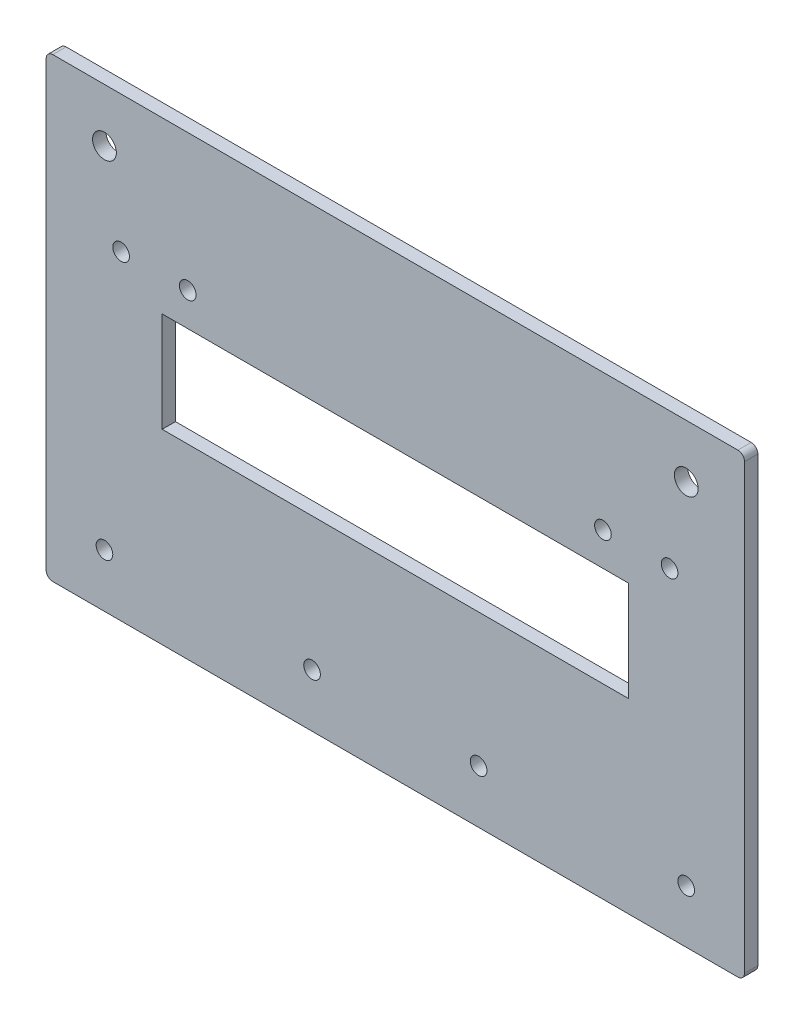
SolidWorks part; units mm, degrees
ref_plane "Front" through (0, 0, 0) normal (0, 0, 1) x (1, 0, 0)
ref_plane "Top" through (0, 0, 0) normal (0, 1, 0) x (1, 0, 0)
ref_plane "Right" through (0, 0, 0) normal (1, 0, 0) x (0, 0, -1)
sketch "Sketch1" plane through (0, 0, 0) normal (0, 0, 1) x (1, 0, 0)
  line L1 (0, 137) -> (209.64, 137)
  line L2 (0, 137) -> (0, 0)
  line L3 (0, 0) -> (209.64, 0)
  line L4 (209.64, 137) -> (209.64, 0)
  line L5 (52.5, 106) -> (52.5, 86)
  line L6 (52.5, 86) -> (34.82, 86)
  line L7 (34.82, 86) -> (34.82, 56)
  line L8 (34.82, 56) -> (174.82, 56)
  line L9 (174.82, 56) -> (174.82, 86)
  line L10 (174.82, 86) -> (157.14, 86)
  line L11 (157.14, 86) -> (157.14, 106)
  line L14 (157.14, 106) -> (52.5, 106)
  line L17 (104.82, 106) -> (104.82, 56) construction
  circle A0 centre (17.5, 16) radius 3.65
  circle A3 centre (192.14, 16) radius 3.65
  circle A5 centre (17.5, 121) radius 3.57
  circle A6 centre (42.5, 96) radius 2.5
  circle A7 centre (22.5, 96) radius 2.5
  circle A8 centre (192.14, 121) radius 3.57
  circle A9 centre (167.14, 96) radius 2.5
  circle A10 centre (187.14, 96) radius 2.5
  point P47 (52.5, 96)
  point P48 (157.14, 96)
  point P54 (104.82, 137)
  dimension "D3" = 5
  dimension "D4" = 5
  dimension "D5" = 5
  dimension "D6" = 5
  dimension "D13" = 7.3
  dimension "D14" = 7.3
  dimension "D17" = 7.14
  dimension "D18" = 7.14
  dimension "D1" = 20
  dimension "D2" = 20
  dimension "D11" = 20
  dimension "D19" = 10
  dimension "D20" = 10
  dimension "D24" = 30
  dimension "D26" = 17.5
  dimension "D29" = 17.5
  dimension "D30" = 16
  dimension "D31" = 16
  dimension "D9" = 140
  dimension "D10" = 104.64
  dimension "D7" = 25
  dimension "D12" = 40
  dimension "D8" = 5
extrude "Boss-Extrude1" add sketch "Sketch1" along normal blind 4
fillet "Fillet1" [suppressed] radius 2
sketch "Sketch2" plane through (0, 0, 4) normal (0, 0, 1) x (1, 0, 0)
  line L0 (11.5, 107) -> (11.5, 85)
  line L1 (11.5, 107) -> (49.82, 107)
  line L2 (11.5, 85) -> (34.82, 85)
  line L4 (198.14, 107) -> (198.14, 85)
  line L5 (52.5, 86) -> (34.82, 86) construction
  line L7 (198.14, 85) -> (174.82, 85)
  line L9 (157.14, 86) -> (157.14, 106) construction
  line L10 (52.5, 106) -> (52.5, 86) construction
  line L11 (34.82, 86) -> (34.82, 56) construction
  line L12 (174.82, 56) -> (174.82, 86) construction
  line L13 (49.82, 107) -> (49.82, 121)
  line L14 (49.82, 121) -> (159.82, 121)
  line L15 (159.82, 121) -> (159.82, 107)
  line L16 (159.82, 107) -> (198.14, 107)
  line L17 (34.82, 56) -> (174.82, 56) construction
  point P4 (104.82, 56)
  point P21 (104.82, 121)
  dimension "D3" = 41
  dimension "D2" = 1
  dimension "D4" = 41
  dimension "D1" = 14
  dimension "D5" = 110
  dimension "D6" = 22
extrude "Cut-Extrude1" [suppressed] cut sketch "Sketch2" against normal through all
sketch "Sketch3" plane through (0, 0, 4) normal (0, 0, 1) x (1, 0, 0)
  line L1 (52.5, 86) -> (157.14, 86)
  line L2 (52.5, 86) -> (52.5, 106)
  line L3 (52.5, 106) -> (157.14, 106)
  line L4 (157.14, 86) -> (157.14, 106)
extrude "Boss-Extrude2" add sketch "Sketch3" against normal blind 4
sketch "Sketch5" plane through (0, 0, 4) normal (0, 0, 1) x (1, 0, 0)
  line L0 (91.82, 48) -> (117.82, 48) construction
  line L1 (91.82, 48) -> (91.82, 22) construction
  line L3 (34.82, 56) -> (174.82, 56) construction
  line L5 (0, 0) -> (209.64, 0) construction
  circle A0 centre (104.82, 35) radius 11
  circle A1 centre (91.82, 48) radius 1.5
  circle A2 centre (117.82, 48) radius 1.5
  circle A3 centre (91.82, 22) radius 1.5
  circle A4 centre (117.82, 22) radius 1.5
  point P10 (104.82, 48)
  point P11 (91.82, 35)
  point P14 (104.82, 0)
  dimension "D3" = 22
  dimension "D1" = 26
  dimension "D2" = 26
  dimension "D4" = 8
extrude "Cut-Extrude3" [suppressed] cut sketch "Sketch5" against normal blind 4
sketch "Sketch6" plane through (0, 0, 4) normal (0, 0, 1) x (1, 0, 0)
  line L0 (79.82, 16) -> (129.82, 16) construction
  line L1 (0, 0) -> (209.64, 0) construction
  circle A0 centre (79.82, 16) radius 3.65
  circle A1 centre (129.82, 16) radius 3.65
  point P4 (104.82, 16)
  point P9 (104.82, 0)
  dimension "D2" = 7.3
  dimension "D3" = 7.3
  dimension "D1" = 50
extrude "Cut-Extrude4" cut sketch "Sketch6" against normal blind 4
sketch "Sketch7" [suppressed] plane through (0, 0, 4) normal (0, 0, 1) x (1, 0, 0)
  line L0 (0, 121) -> (0, 0) construction
  line L1 (209.64, 0) -> (209.64, 121) construction
  line L2 (34.82, 48) -> (174.82, 48) construction
  circle A0 centre (5, 43.5) radius 1.5
  circle A1 centre (5, 32.5) radius 1.5
  circle A2 centre (204.64, 43.5) radius 1.5
  circle A3 centre (204.64, 32.5) radius 1.5
  dimension "D3" = 5
  dimension "D4" = 3
  dimension "D5" = 3
  dimension "D6" = 3
  dimension "D7" = 3
  dimension "D1" = 5
  dimension "D2" = 11
  dimension "D8" = 4.5
extrude "Cut-Extrude5" [suppressed] cut sketch "Sketch7" against normal blind 10
sketch "Sketch8" [suppressed] plane through (0, 0, 4) normal (0, 0, 1) x (1, 0, 0)
  line L1 (34.82, 56) -> (174.82, 56)
  line L2 (34.82, 56) -> (34.82, 40)
  line L3 (34.82, 40) -> (174.82, 40)
  line L4 (174.82, 56) -> (174.82, 40)
  dimension "D1" = 16
extrude "Cut-Extrude6" [suppressed] cut sketch "Sketch8" against normal blind 10
fillet "Fillet2" [suppressed] radius 40
sketch "Sketch9" plane through (0, 0, 4) normal (0, 0, 1) x (1, 0, 0)
  line L0 (209.64, 137) -> (0, 137) construction
  line L1 (0, 137) -> (17, 137)
  line L2 (0, 137) -> (0, 130)
  line L3 (0, 130) -> (17, 130)
  line L4 (17, 137) -> (17, 130)
  line L5 (209.64, 137) -> (192.64, 137)
  line L6 (209.64, 137) -> (209.64, 130)
  line L7 (209.64, 130) -> (192.64, 130)
  line L8 (192.64, 137) -> (192.64, 130)
  line L9 (209.64, 0) -> (192.64, 0)
  line L10 (209.64, 0) -> (209.64, 7)
  line L11 (209.64, 7) -> (192.64, 7)
  line L12 (192.64, 0) -> (192.64, 7)
  line L13 (0, 0) -> (17, 0)
  line L14 (0, 0) -> (0, 7)
  line L15 (0, 7) -> (17, 7)
  line L16 (17, 0) -> (17, 7)
  line L17 (0, 137) -> (0, 0) construction
  line L18 (209.64, 0) -> (209.64, 137) construction
  line L19 (0, 0) -> (209.64, 0) construction
  dimension "D1" = 7
  dimension "D2" = 17
  dimension "D3" = 17
  dimension "D4" = 7
extrude "Cut-Extrude7" [suppressed] cut sketch "Sketch9" against normal through all
fillet "Fillet3" [suppressed] radius 2
fillet "Fillet4" [suppressed] radius 2
fillet "Fillet5" radius 2 4 edges at (0, 0, 2) (0, 137, 2) (209.64, 137, 2) (209.64, 0, 2)
sketch "Sketch10" plane through (0, 0, 4) normal (0, 0, 1) x (1, 0, 0)
  line L1 (8.6284, 23.2942) -> (201.5012, 23.2942)
  line L2 (8.6284, 23.2942) -> (8.6284, 8.7058)
  line L3 (8.6284, 8.7058) -> (201.5012, 8.7058)
  line L4 (201.5012, 23.2942) -> (201.5012, 8.7058)
  circle A0 centre (17.5, 16) radius 2.5
  circle A1 centre (192.14, 16) radius 2.5
  circle A2 centre (129.82, 16) radius 2.5
  circle A3 centre (79.82, 16) radius 2.5
  point P16 (8.6284, 16)
  dimension "D3" = 5
  dimension "D4" = 5
  dimension "D1" = 5
  dimension "D2" = 5
extrude "Boss-Extrude3" add sketch "Sketch10" against normal through all contours A0 | A3 | A2 | A1 region at (105.0718, 16, 4)
sketch "Sketch11" [suppressed] plane through (0, 0, 4) normal (0, 0, 1) x (1, 0, 0)
  line L0 (79.82, 16) -> (129.82, 16) construction
  line L1 (7.3641, 23.5) -> (202.2759, 23.5)
  line L2 (7.3641, 23.5) -> (7.3641, 8.5)
  line L3 (7.3641, 8.5) -> (202.2759, 8.5)
  line L4 (202.2759, 23.5) -> (202.2759, 8.5)
  circle A0 centre (17.5, 16) radius 2.5
  circle A1 centre (192.14, 16) radius 2.5
  point P12 (104.82, 23.5)
  point P13 (202.2759, 16)
  point P15 (104.82, 16)
  dimension "D3" = 5
  dimension "D4" = 5
  dimension "D1" = 15
  dimension "D2" = 194.9117
extrude "Boss-Extrude4" [suppressed] add sketch "Sketch11" against normal through all
equation "\"D2@Sketch1\"=\"D1@Sketch1\""
equation "\"D4@Sketch1\"=\"D3@Sketch1\""
equation "\"D5@Sketch1\"=\"D3@Sketch1\""
equation "\"D6@Sketch1\"=\"D3@Sketch1\""
equation "\"D13@Sketch1\"=\"D14@Sketch1\""
equation "\"D17@Sketch1\"=\"D18@Sketch1\""
equation "\"D19@Sketch1\"=\"D20@Sketch1\""
equation "\"D29@Sketch1\"=\"D26@Sketch1\""
equation "\"D3@Sketch6\"=\"D2@Sketch6\""
equation "\"D30@Sketch1\"=\"D31@Sketch1\""
equation "\"D3@Sketch2\"=\"D4@Sketch2\""
equation "\"D3@Sketch7\"=\"D1@Sketch7\""
equation "\"D5@Sketch7\"=\"D4@Sketch7\""
equation "\"D6@Sketch7\"=\"D4@Sketch7\""
equation "\"D7@Sketch7\"=\"D4@Sketch7\""
equation "\"D26@Sketch1\"=17.5"
equation "\"D3@Sketch9\"=\"D2@Sketch9\""
equation "\"D4@Sketch9\"=\"D1@Sketch9\""
equation "\"D2@Sketch10\"=\"D1@Sketch10\""
equation "\"D3@Sketch10\"=\"D1@Sketch10\""
equation "\"D4@Sketch10\"=\"D1@Sketch10\""
equation "\"D3@Sketch11\"=\"D4@Sketch11\""
